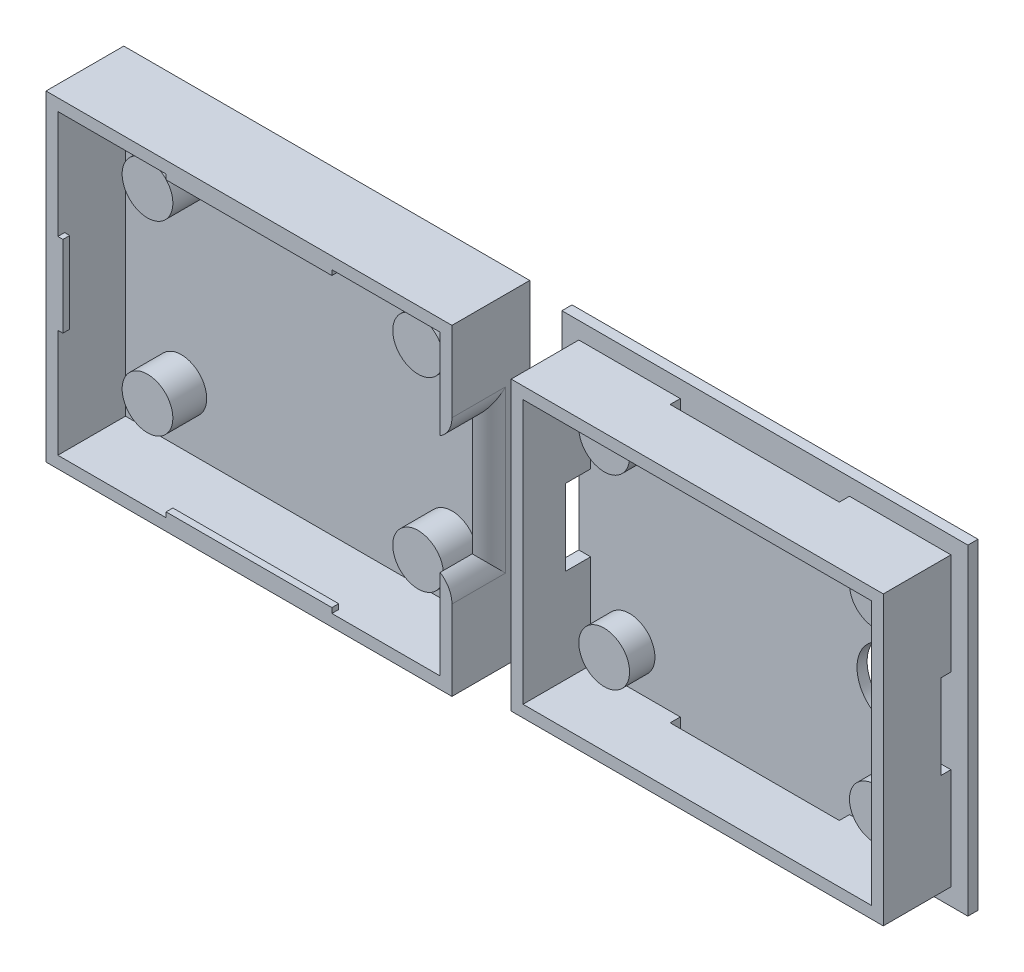
SolidWorks part; units mm, degrees
ref_plane "Alzado" through (0, 0, 0) normal (0, 0, 1) x (1, 0, 0)
ref_plane "Planta" through (0, 0, 0) normal (0, 1, 0) x (1, 0, 0)
ref_plane "Vista lateral" through (0, 0, 0) normal (1, 0, 0) x (0, 0, -1)
sketch "Croquis1" plane through (0, 0, 0) normal (0, 0, 1) x (1, 0, 0)
  line L0 (24, -19) -> (24, 19)
  line L1 (-24, 19) -> (24, 19)
  line L2 (-24, 19) -> (-24, -19)
  line L3 (-24, -19) -> (24, -19)
  line L5 (-24, 19) -> (24, -19) construction
  line L6 (-24, -19) -> (24, 19) construction
  line L7 (-20, 15) -> (20, 15) construction
  line L8 (-20, 15) -> (-20, -15) construction
  line L9 (-20, -15) -> (20, -15) construction
  line L10 (20, 15) -> (20, -15) construction
  line L11 (-20, 15) -> (20, -15) construction
  line L12 (-20, -15) -> (20, 15) construction
  line L13 (-77, 19) -> (-29, 19)
  line L14 (-77, 19) -> (-77, -19)
  line L15 (-77, -19) -> (-29, -19)
  line L16 (-29, 19) -> (-29, -19)
  line L17 (-77, 19) -> (-29, -19) construction
  line L18 (-77, -19) -> (-29, 19) construction
  circle A0 centre (15.1396, -0.0718) radius 4.25
  point P0 (0, 0)
  point P6 (0, 0)
  point P13 (-53, 0)
  dimension "D7" = 8.5
  dimension "D1" = 48
  dimension "D2" = 30
  dimension "D3" = 38
  dimension "D4" = 40
  dimension "D5" = 35.1396
  dimension "D6" = 14.9282
  dimension "D8" = 5
extrude "Saliente-Extruir1" add sketch "Croquis1" along normal blind 1.2
sketch "Croquis2" plane through (0, 0, 1.2) normal (0, 0, 1) x (1, 0, 0)
  line L0 (-26.5, 19) -> (-26.5, -19) construction
  line L1 (-29, 19) -> (-24, 19) construction
  line L4 (20.6, 15.6) -> (-20.6, 15.6)
  line L5 (-20.6, 15.6) -> (-20.6, 4.5)
  line L6 (-20.6, -15.6) -> (20.6, -15.6)
  line L7 (20.6, -15.6) -> (20.6, 15.6)
  line L8 (-22, -17) -> (22, -17)
  line L9 (22, -17) -> (22, 17)
  line L10 (22, 17) -> (-22, 17)
  line L11 (-22, 17) -> (-22, -17)
  line L12 (-22, -17) -> (22, -17)
  line L13 (22, -17) -> (22, 17)
  line L14 (22, 17) -> (-22, 17)
  line L15 (-22, 17) -> (-22, 4.5)
  line L16 (-22, 4.5) -> (-20.6, 4.5)
  line L17 (-22, -4.5) -> (-20.6, -4.5)
  line L18 (-22, -4.5) -> (-22, -17)
  line L19 (-22, 17) -> (-22, -17) construction
  line L20 (-20.6, -4.5) -> (-20.6, -15.6)
  line L21 (-20.6, 15.6) -> (-20.6, -15.6) construction
  line L22 (-20, 15) -> (20, 15) construction
  line L24 (-20, 15) -> (-20, -15) construction
  line L25 (20, 15) -> (20, -15) construction
  line L26 (-20, -15) -> (20, -15) construction
  line L31 (-29, -19) -> (-29, 19)
  line L32 (-29, 19) -> (-77, 19)
  line L33 (-77, 19) -> (-77, -19)
  line L34 (-77, -19) -> (-29, -19)
  line L35 (-29, -19) -> (-29, -7)
  line L36 (-29, 19) -> (-77, 19)
  line L37 (-77, 19) -> (-77, -19)
  line L38 (-77, -19) -> (-29, -19)
  line L41 (-30.4, 6.9982) -> (-30.4, 17.6)
  line L42 (-29, 7) -> (-29, 19)
  line L43 (-30.4, -17.6) -> (-30.4, 17.6)
  line L44 (-30.4, 17.6) -> (-75.6, 17.6)
  line L45 (-75.6, 17.6) -> (-75.6, -17.6)
  line L46 (-75.6, -17.6) -> (-30.4, -17.6)
  line L47 (-30.4, -17.6) -> (-30.4, -7.0018)
  line L48 (-30.4, 17.6) -> (-75.6, 17.6)
  line L49 (-75.6, 17.6) -> (-75.6, -17.6)
  line L50 (-75.6, -17.6) -> (-30.4, -17.6)
  line L51 (-29, 7) -> (-29, -7)
  line L52 (-30.4, 6.9982) -> (-30.4, -7.0018)
  circle A0 centre (-16, 11) radius 3
  circle A1 centre (16, 11) radius 3
  circle A2 centre (-16, -11) radius 3
  circle A3 centre (16, -11) radius 3
  circle A4 centre (-69, 11) radius 3
  circle A5 centre (-69, -11) radius 3
  circle A6 centre (-37, -11) radius 3
  circle A7 centre (-37, 11) radius 3
  dimension "D5" = 6
  dimension "D3" = 4.5
  dimension "D4" = 4.5
  dimension "D6" = 4
  dimension "D7" = 4
  dimension "D8" = 4
  dimension "D9" = 4
  dimension "D10" = 0
  dimension "D1" = 2
  dimension "D2" = 1.4
  dimension "D11" = 1.4
extrude "Saliente-Extruir2" add sketch "Croquis2" along normal blind 8 contours L51 L42 L36 L37 L38 L35 L41 L52 L47 L50 L49 L48 | A6 | A5 | A4 | A7 | A0 | A2 | A3 | A1 | L14 L15 L16 L5 L4 L7 L6 L20 L17 L18 L12 L13 region at (-53, -18.3878, 1.2) region at (-16, 11, 1.2) region at (16, 11, 1.2) region at (-16, -11, 1.2) region at (16, -11, 1.2) region at (-69, 11, 1.2) region at (-69, -11, 1.2) region at (-37, -11, 1.2) region at (-37, 11, 1.2)
sketch "Croquis3" plane through (0, -17, 0) normal (0, -1, 0) x (1, 0, 0)
  line L0 (-10, 1.2) -> (-10, 2.4)
  line L1 (-24, 1.2) -> (24, 1.2) construction
  line L2 (-10, 2.4) -> (10, 2.4)
  line L3 (10, 2.4) -> (10, 1.2)
  line L4 (-22, 1.2) -> (22, 1.2) construction
  line L5 (10, 1.2) -> (-10, 1.2)
  point P4 (0, 2.4)
  dimension "D1" = 20
  dimension "D2" = 1.2
extrude "Cortar-Extruir1" cut sketch "Croquis3" against normal up to surface (34 mm away) up to face at (0, 17, 5.2)
sketch "Croquis4" plane through (0, 0, 9.2) normal (0, 0, 1) x (1, 0, 0)
  circle A5 centre (16, -11) radius 3
  circle A6 centre (-16, -11) radius 3
  circle A7 centre (-16, 11) radius 3
  circle A8 centre (16, 11) radius 3
  circle A9 centre (16, 11) radius 3
  dimension "D1" = 0
extrude "Cortar-Extruir2" cut sketch "Croquis4" against normal blind 5
sketch "Croquis7" plane through (0, 0, 9.2) normal (0, 0, 1) x (1, 0, 0)
  line L0 (-30.4, 7) -> (-29, 7)
  line L3 (-30.4, -17.6) -> (-30.4, 17.6) construction
  line L4 (-29, 19) -> (-29, -19) construction
  line L6 (-29, 7) -> (-29, -7)
  line L7 (-29, -7) -> (-30.4, -7)
  line L8 (-30.4, -7) -> (-30.4, 7)
  point P6 (-29, 0)
  dimension "D1" = 14
extrude "Cortar-Extruir3" cut sketch "Croquis7" against normal blind 3.8
sketch "Croquis8" plane through (22, 0, 0) normal (1, 0, 0) x (0, 0, -1)
  line L0 (-1.2, 5) -> (-1.2, -5)
  line L1 (-1.2, -19) -> (-1.2, 19) construction
  line L2 (-1.2, -17) -> (-1.2, 17) construction
  line L3 (-1.2, -5) -> (-2.4, -5)
  line L4 (-2.4, -5) -> (-2.4, 5)
  line L5 (-2.4, 5) -> (-1.2, 5)
  point P6 (-1.2, 0)
  dimension "D1" = 10
  dimension "D2" = 1.2
extrude "Cortar-Extruir4" cut sketch "Croquis8" against normal up to next
sketch "Croquis9" plane through (0, 0, 9.2) normal (0, 0, 1) x (1, 0, 0)
  line L0 (-75.6, 4.8) -> (-75, 4.8)
  line L2 (-75.6, 17.6) -> (-75.6, -17.6) construction
  line L3 (-75, 4.8) -> (-75, -4.8)
  line L5 (-75, -4.8) -> (-75.6, -4.8)
  line L6 (-62.8, -17.6) -> (-62.8, -17)
  line L8 (-62.8, -17) -> (-43.2, -17)
  line L9 (-43.2, -17) -> (-43.2, -17.6)
  line L10 (-75.6, -17.6) -> (-30.4, -17.6) construction
  line L11 (-75.6, 17.6) -> (-75.6, -17.6) construction
  line L14 (-62.8, -17.6) -> (-43.2, -17.6)
  line L15 (-62.8, 17.6) -> (-62.8, 17)
  line L16 (-30.4, 17.6) -> (-75.6, 17.6) construction
  line L17 (-62.8, 17) -> (-43.2, 17)
  line L18 (-43.2, 17) -> (-43.2, 17.6)
  line L19 (-75.6, -17.6) -> (-30.4, -17.6) construction
  line L20 (-75.6, 4.8) -> (-75.6, -4.8)
  line L21 (-30.4, 17.6) -> (-75.6, 17.6) construction
  line L22 (-43.2, 17.6) -> (-62.8, 17.6)
  line L23 (-29, 19) -> (-77, 19) construction
  point P4 (-75, 0)
  point P14 (-53, -17.6)
  point P19 (-53, -17)
  point P24 (-53, 17)
  point P30 (-53, 19)
  dimension "D1" = 0.6
  dimension "D2" = 9.6
  dimension "D3" = 0.6
  dimension "D4" = 19.6
  dimension "D5" = 0.6
  dimension "D6" = 19.6
extrude "Saliente-Extruir3" add sketch "Croquis9" against normal blind 0.8
sketch "Croquis11" plane through (0, 0, 9.2) normal (0, 0, 1) x (1, 0, 0)
  circle A0 centre (-37, -11) radius 3 construction
  circle A1 centre (-37, 11) radius 3 construction
  circle A2 centre (-69, 11) radius 3 construction
  circle A3 centre (-69, -11) radius 3 construction
  circle A4 centre (-37, -11) radius 3
  circle A5 centre (-37, 11) radius 3
  circle A6 centre (-69, 11) radius 3
  circle A7 centre (-69, -11) radius 3
extrude "Cortar-Extruir5" cut sketch "Croquis11" against normal blind 4
sketch "Croquis12" plane through (0, 0, 1.2) normal (0, 0, 1) x (1, 0, 0)
  line L0 (-22, -7) -> (-22, 7)
  line L1 (-22, -4.5) -> (-22, -17) construction
  line L2 (-22, 17) -> (-22, 4.5) construction
  line L3 (-22, -7) -> (-24, -7)
  line L4 (-24, 19) -> (-24, -19) construction
  line L5 (-24, -7) -> (-24, 7)
  line L6 (-24, 7) -> (-22, 7)
  point P6 (-22, 0)
  dimension "D1" = 14
extrude "Cortar-Extruir6" cut sketch "Croquis12" against normal up to next
fillet "Redondeo1" radius 3 2 edges at (-29, -7, 7.3) (-29, 7, 7.3)
fillet "Redondeo2" radius 3 2 edges at (-24, -7, 0.6) (-24, 7, 0.6)
sketch "Croquis13" plane through (0, 0, 9.2) normal (0, 0, 1) x (1, 0, 0)
  line L0 (-22, 4.5) -> (-22, -4.5)
  line L1 (-22, -4.5) -> (-20.6, -4.5)
  line L2 (-20.6, -4.5) -> (-20.6, 4.5)
  line L3 (-20.6, 4.5) -> (-22, 4.5)
extrude "Saliente-Extruir4" add sketch "Croquis13" against normal blind 5
fillet "Redondeo3" radius 3 1 edges at (-29, 0, 5.4)
